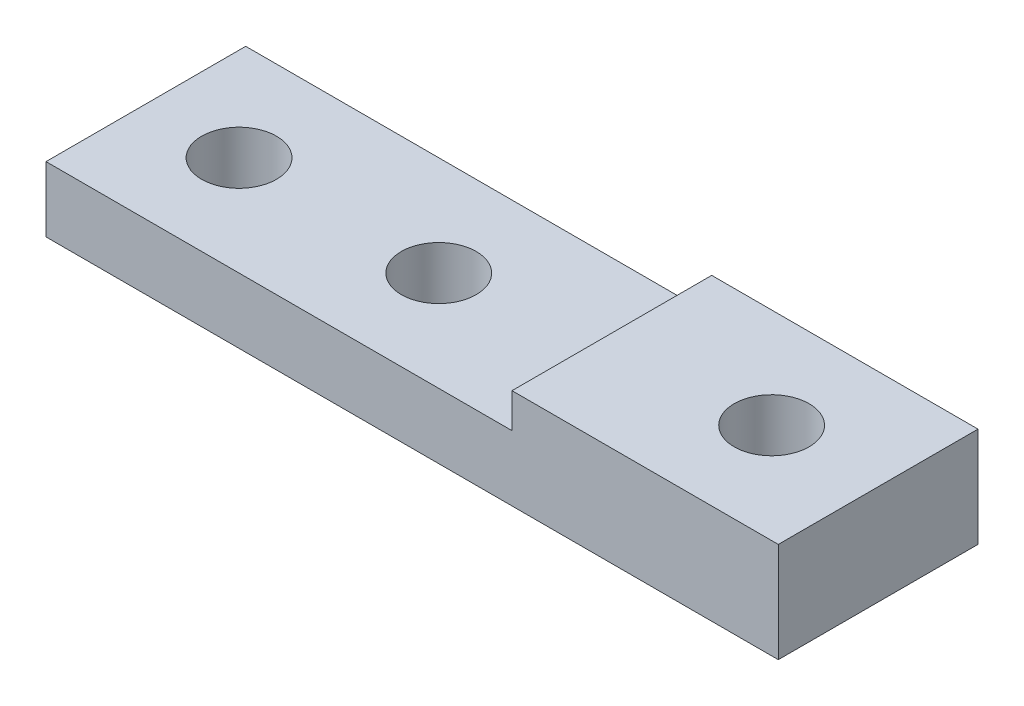
SolidWorks part; units mm, degrees
ref_plane "Front Plane" through (0, 0, 0) normal (0, 0, 1) x (1, 0, 0)
ref_plane "Top Plane" through (0, 0, 0) normal (0, 1, 0) x (1, 0, 0)
ref_plane "Right Plane" through (0, 0, 0) normal (1, 0, 0) x (0, 0, -1)
sketch "Sketch1" plane through (0, 0, 0) normal (0, 1, 0) x (1, 0, 0)
  line L1 (-34.925, 9.525) -> (34.925, 9.525)
  line L2 (-34.925, 9.525) -> (-34.925, -9.525)
  line L3 (-34.925, -9.525) -> (34.925, -9.525)
  line L4 (34.925, 9.525) -> (34.925, -9.525)
  line L5 (-34.925, 9.525) -> (34.925, -9.525) construction
  line L6 (-34.925, -9.525) -> (34.925, 9.525) construction
  point P4 (0, 0)
  point P5 (0, 0)
  point P6 (-6.985, 0)
  point P7 (24.765, 0)
  point P8 (-26.035, 0)
  point P11 (-34.925, 0)
  dimension "D1" = 19.05
  dimension "D2" = 50.8
  dimension "D3" = 19.05
  dimension "D4" = 10.16
  dimension "D5" = 69.85
extrude "Boss-Extrude1" add sketch "Sketch1" along normal blind 6.223
sketch "Sketch4" plane through (0, 6.223, 0) normal (0, 1, 0) x (1, 0, 0)
  line L0 (-34.925, -9.525) -> (34.925, -9.525) construction
  line L1 (34.925, 9.525) -> (9.525, 9.525)
  line L2 (34.925, 9.525) -> (34.925, -9.525)
  line L3 (34.925, -9.525) -> (9.525, -9.525)
  line L4 (9.525, 9.525) -> (9.525, -9.525)
  line L5 (34.925, 9.525) -> (9.525, -9.525) construction
  line L6 (34.925, -9.525) -> (9.525, 9.525) construction
  point P4 (22.225, 0)
  dimension "D1" = 25.4
extrude "Boss-Extrude2" add sketch "Sketch4" along normal blind 3.302
hole_wizard "1/4 Clearance Hole2" positions "Sketch5" profile "Sketch6" hole size "1/4" standard "ANSI Inch" end condition through all
sketch "Sketch5" plane through (0, 0, 0) normal (0, -1, 0) x (-1, 0, 0)
  point P0 (-24.765, 0)
  point P3 (6.985, 0)
  point P6 (26.035, 0)
sketch "Sketch6" plane through (24.765, 0, 0) normal (1, 0, 0) x (0, 0, -1)
  line L0 (0, 0) -> (0, 9.525)
  line L1 (0, 9.525) -> (3.5712, 9.525)
  line L2 (3.5712, 9.525) -> (3.5712, 0)
  line L5 (3.5712, 0) -> (0, 0)
  line L11 (0, -6.35) -> (0, 107.95) construction
  dimension "Thru Hole Dia." = 7.1425
  dimension "Thru Hole Depth" = 9.525
